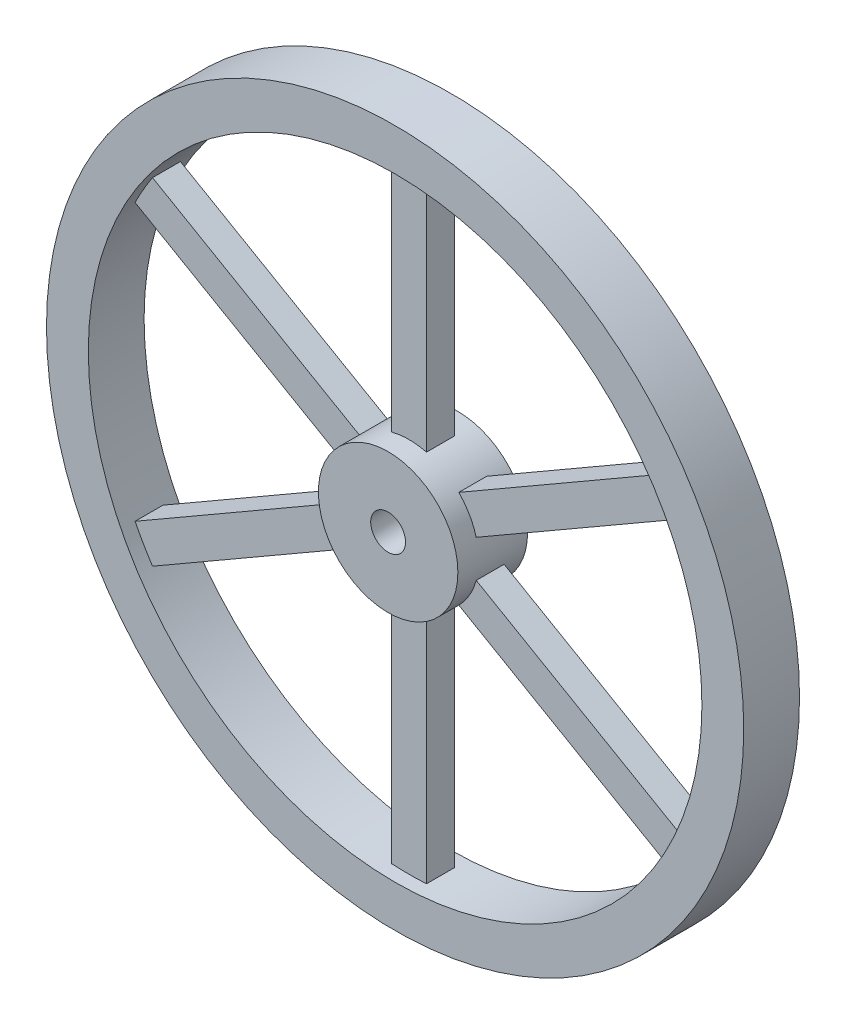
SolidWorks part; units mm, degrees
material "Gray Cast Iron"
ref_plane "Front Plane" through (0, 0, 0) normal (0, 0, 1) x (1, 0, 0)
ref_plane "Top Plane" through (0, 0, 0) normal (0, 1, 0) x (1, 0, 0)
ref_plane "Right Plane" through (0, 0, 0) normal (1, 0, 0) x (0, 0, -1)
sketch "Sketch1" plane through (0, 0, 0) normal (0, 0, 1) x (1, 0, 0)
  circle A0 centre (0, 0) radius 50
  circle A1 centre (0, 0) radius 44
  dimension "D1" = 100
  dimension "D2" = 88
extrude "Boss-Extrude1" add sketch "Sketch1" along normal mid plane 8
sketch "Sketch2" plane through (0, 0, 0) normal (0, 0, 1) x (1, 0, 0)
  circle A0 centre (0, 0) radius 10
  dimension "D1" = 20
extrude "Boss-Extrude2" add sketch "Sketch2" along normal mid plane 10
sketch "Sketch3" plane through (0, 0, 0) normal (0, 0, 1) x (1, 0, 0)
  line L0 (-2.5, 9) -> (2.5, 9)
  line L1 (2.5, 9) -> (2.5, 45)
  line L2 (2.5, 45) -> (-2.5, 45)
  line L3 (-2.5, 45) -> (-2.5, 9)
  dimension "D1" = 5
  dimension "D2" = 36
extrude "Boss-Extrude3" add sketch "Sketch3" along normal mid plane 4
sketch "Sketch4" plane through (0, 0, 0) normal (0, 0, 1) x (1, 0, 0)
  circle A0 centre (0, 0) radius 2.5
  dimension "D1" = 5
extrude "Cut-Extrude1" cut sketch "Sketch4" against normal mid plane 12
pattern_circular "CirPattern1" count 6 over 360 about axis through (0, 0, 5) along (0, 0, 1) of "Boss-Extrude3"
